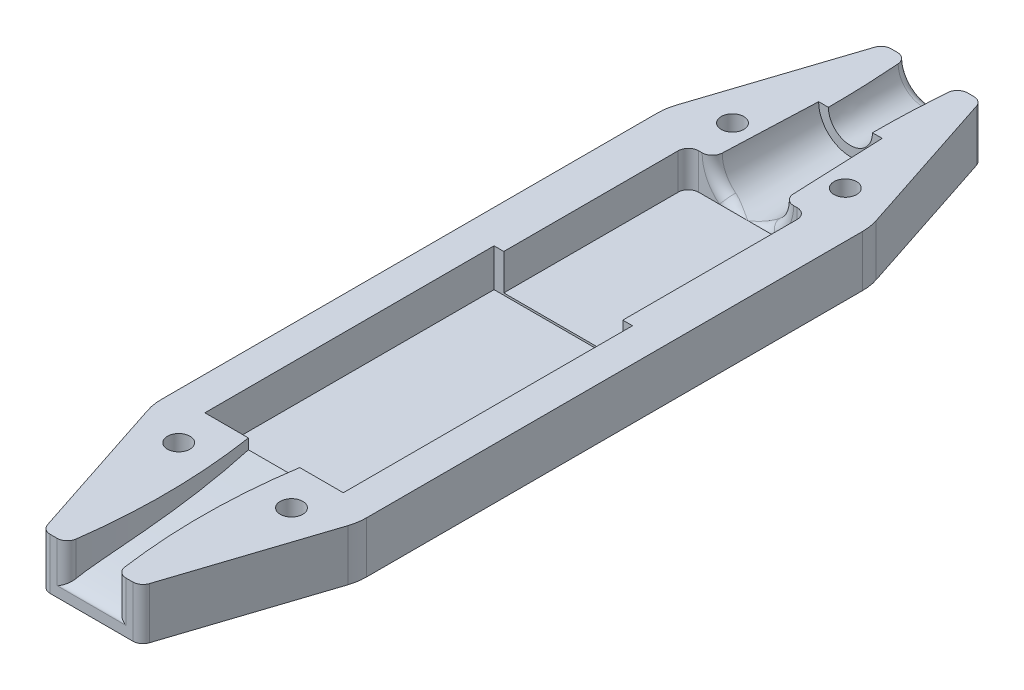
SolidWorks part; units mm, degrees
ref_plane "Ebene vorne" through (0, 0, 0) normal (0, 0, 1) x (1, 0, 0)
ref_plane "Ebene oben" through (0, 0, 0) normal (0, 1, 0) x (1, 0, 0)
ref_plane "Ebene rechts" through (0, 0, 0) normal (1, 0, 0) x (0, 0, -1)
sketch "Skizze1" plane through (0, 0, 0) normal (0, 0, 1) x (1, 0, 0)
  line L0 (0, 2.5) -> (0, -2.5)
  line L1 (-10, -2.5) -> (10, -2.5)
  line L2 (-10, -2.5) -> (-10, 2.5)
  line L3 (-10, 2.5) -> (10, 2.5)
  line L4 (10, -2.5) -> (10, 2.5)
  point P7 (0, 0)
extrude "Aufsatz-Linear austragen1" add sketch "Skizze1" along normal blind 30 contours L3 L2 L1 L0 | L1 L4 L3 L0 region at (5, 0, 0) region at (-5, 0, 0)
sketch "Skizze4" plane through (0, 0, 0) normal (0, 0, -1) x (-1, 0, 0)
  line L0 (0, 0) -> (0, 2.5)
  line L1 (10, 2.5) -> (-10, 2.5) construction
sketch "Skizze5" plane through (0, 2.5, 0) normal (0, 1, 0) x (1, 0, 0)
  line L0 (-6.75, 0) -> (6.75, 0)
  line L1 (-10, 0) -> (10, 0) construction
  line L2 (-6.75, 0) -> (-6.75, -28.2)
  line L3 (-6.75, -28.2) -> (6.75, -28.2)
  line L4 (6.75, -28.2) -> (6.75, 0)
  point P4 (0, 0)
extrude "Schnitt-Linear austragen1" cut sketch "Skizze5" against normal blind 3.7
sketch "Skizze7" plane through (0, 2.5, 0) normal (0, 1, 0) x (1, 0, 0)
  line L0 (-10, -30) -> (10, -30)
  line L1 (10, -30) -> (4.75, -46)
  line L2 (4.75, -46) -> (-4.75, -46)
  line L3 (-4.75, -46) -> (-10, -30)
  line L4 (0, -30) -> (0, -46)
  line M9 (-10, -30) -> (10, -30)
extrude "Aufsatz-Linear austragen3" add sketch "Skizze7" against normal blind 5 contours L4 L3 L2 M9 | L0 L4 L2 L1 region at (-3.8432, 2.5, 37.0508) region at (3.8432, 2.5, 37.0508)
sketch "Skizze8" plane through (0, 2.5, 0) normal (0, 1, 0) x (1, 0, 0)
  line L0 (-4.75, -46) -> (4.75, -46)
  line L1 (-6.75, -28.2) -> (6.75, -28.2) construction
  line L2 (-2.5, -46) -> (2.5, -46)
  line L3 (-2.5, -46) -> (-2.5, -28.2)
  line L4 (-2.5, -28.2) -> (2.5, -28.2)
  line L5 (2.5, -46) -> (2.5, -28.2)
  line L6 (-2.5, -46) -> (2.5, -28.2)
  line L7 (-60, -37.1) -> (60, -37.1)
  line L8 (4.75, -46) -> (-4.75, -46) construction
  line L10 (-1.8153, -37.1) -> (1.8153, -37.1)
  arc A0 (-2.5, -28.2) -> (-2.5, -46) centre (-60, -37.1) cw
  arc A1 (2.5, -46) -> (2.5, -28.2) centre (60, -37.1) cw
  point P12 (0, -46)
  point P13 (0, -46)
  point P14 (0, -37.1)
  point P15 (0, -37.1)
  line M16 (6.75, -28.2) -> (-6.75, -28.2)
extrude "Schnitt-Linear austragen3" cut sketch "Skizze8" against normal blind 4 contours A0 L7 L6 M16 | L7 A1 L6 | L0 A1 L7 L6 | L7 A0 L6 region at (0.3237, 2.5, 42.2671) region at (-1.3443, 2.5, 39.8514) region at (-0.3237, 2.5, 31.9329) region at (1.3443, 2.5, 34.3486)
sketch "Skizze9" plane through (0, 0, 0) normal (1, 0, 0) x (0, 0, -1)
  line L0 (-28.2, -1.5) -> (-28.2, 1.5)
  line L1 (-28.2, -1.2) -> (-28.2, 2.5) construction
  line L2 (-28.2, -1.5) -> (-46, -1.5)
  parabola Q0 (-42.3553, -2.8575) -> (-28.2, 1.5) focus (-45.8736, -1.5) apex (-46, -1.5)
extrude "Aufsatz-Linear austragen4" add sketch "Skizze9" along normal mid plane 6 contours Q0 L2 L0 region at (0, -0.375, 35.32)
sketch "Skizze10" plane through (0, 2.5, 0) normal (0, 1, 0) x (1, 0, 0)
  line L0 (10, -30) -> (-10, -30) construction
  line L1 (5.5, -30) -> (-5.5, -30)
  line L2 (5.5, -30) -> (5.5, -32)
  line L3 (-5.5, -30) -> (-5.5, -32)
  line L4 (-5.5, -32) -> (5.5, -32)
  circle A0 centre (5.5, -32) radius 1.1
  circle A1 centre (-5.5, -32) radius 1.1
  point P6 (0, -30)
  point P7 (0, -30)
extrude "Schnitt-Linear austragen4" cut sketch "Skizze10" against normal through all contours L4 A0 L2 | L3 A1 L4 | L4 A1 L3 | L2 A0 L4 region at (5.6556, 2.5, 32.1556) region at (5.0331, 2.5, 31.5331) region at (-5.0331, 2.5, 31.5331) region at (-5.6556, 2.5, 32.1556)
sketch "Skizze11" plane through (0, -2.5, 0) normal (0, -1, 0) x (1, 0, 0)
  line L1 (-3.0751, 32) -> (-4.2876, 34.1)
  line L2 (-4.2876, 34.1) -> (-6.7124, 34.1)
  line L3 (-6.7124, 34.1) -> (-7.9249, 32)
  line L4 (-7.9249, 32) -> (-6.7124, 29.9)
  line L5 (-6.7124, 29.9) -> (-4.2876, 29.9)
  line L6 (-4.2876, 29.9) -> (-3.0751, 32)
  line L7 (3.0751, 32) -> (4.2876, 29.9)
  line L8 (4.2876, 29.9) -> (6.7124, 29.9)
  line L9 (6.7124, 29.9) -> (7.9249, 32)
  line L10 (7.9249, 32) -> (6.7124, 34.1)
  line L11 (6.7124, 34.1) -> (4.2876, 34.1)
  line L12 (4.2876, 34.1) -> (3.0751, 32)
  circle A0 centre (-5.5, 32) radius 2.1 construction
  circle A1 centre (5.5, 32) radius 2.1 construction
extrude "Schnitt-Linear austragen5" cut sketch "Skizze11" against normal blind 1.6
sketch "Skizze12" plane through (0, 0, 0) normal (0, 0, -1) x (-1, 0, 0)
  line L1 (-10, -2.5) -> (10, -2.5)
  line L2 (-10, -2.5) -> (-10, 2.5)
  line L3 (-10, 2.5) -> (10, 2.5)
  line L4 (10, -2.5) -> (10, 2.5)
extrude "Aufsatz-Linear austragen5" add sketch "Skizze12" along normal blind 20
sketch "Skizze13" plane through (0, 2.5, 0) normal (0, 1, 0) x (1, 0, 0)
  line L0 (0, 20) -> (0, 37.0129)
  line L1 (-10, 20) -> (10, 20) construction
  line L2 (4.75, 37.0129) -> (-4.75, 37.0129)
  line L3 (4.75, 37.0129) -> (10, 20)
  line L4 (10, 20) -> (-10, 20)
  line L5 (-10, 20) -> (-4.75, 37.0129)
  point P8 (0, 37.0129)
sketch "Skizze14" plane through (0, 2.5, 0) normal (0, 1, 0) x (1, 0, 0)
  line L1 (5.8, 18) -> (-5.8, 18)
  line L2 (5.8, 18) -> (5.8, 0)
  line L3 (5.8, 0) -> (-5.8, 0)
  line L4 (-5.8, 18) -> (-5.8, 0)
  point P4 (0, 0)
extrude "Schnitt-Linear austragen6" cut sketch "Skizze14" against normal blind 3.5
sketch "Skizze16" plane through (0, 2.5, 0) normal (0, 1, 0) x (1, 0, 0)
  line L0 (0, 20) -> (0, 36)
  line L1 (-10, 20) -> (10, 20) construction
  line L2 (10, 20) -> (4.75, 36)
  line L3 (-10, 20) -> (-4.75, 36)
  line L4 (-4.75, 36) -> (4.75, 36)
  line L5 (10, 20) -> (-10, 20)
  point P12 (0, 36)
  line M13 (10, 20) -> (-10, 20)
extrude "Aufsatz-Linear austragen6" add sketch "Skizze16" against normal blind 5 contours L4 L0 L2 M13 | L4 L3 L0 M13 region at (-3.8432, 2.5, -27.0508) region at (3.8432, 2.5, -27.0508)
sketch "Skizze17" plane through (0, 2.5, 0) normal (0, 1, 0) x (1, 0, 0)
  line L0 (0, 18) -> (0, 28)
  line L1 (5.8, 18) -> (-5.8, 18) construction
  line L2 (0, 28) -> (3.1, 28)
  line L3 (3.1, 28) -> (3.5, 18)
  line L4 (5.8, 18) -> (-5.8, 18) construction
  line L5 (3.5, 18) -> (0, 18)
  line L6 (0, 28) -> (0, 36)
  line L7 (-4.75, 36) -> (4.75, 36) construction
  line L8 (0, 36) -> (2.499, 36)
  line L9 (0, 28) -> (2.15, 28)
  parabola Q0 (2.499, 36) -> (2.15, 28) focus (48, 28) apex (2.15, 28)
revolve "Schnitt-Rotation1" cut sketch "Skizze17" angle 360 about L6 region at (1.652, 2.5, -22.899) region at (1.1355, 2.5, -32.1027)
fillet "Verrundung1" radius 1 2 edges at (2.4749, 0.0251, -18) (-2.4749, 0.0251, -18)
fillet "Verrundung2" radius 1 2 edges at (-5.8, 0.75, -18) (5.8, 0.75, -18)
sketch "Skizze18" plane through (0, 2.5, 0) normal (0, 1, 0) x (1, 0, 0)
  line L0 (10, 20) -> (-10, 20)
  line L2 (5.5, 22) -> (-5.5, 22)
  line L3 (5.5, 22) -> (5.5, 20)
  line L4 (5.5, 20) -> (-5.5, 20)
  line L5 (-5.5, 22) -> (-5.5, 20)
  circle A0 centre (5.5, 22) radius 1.1
  circle A1 centre (-5.5, 22) radius 1.1
  point P8 (0, 20)
  point P9 (0, 20)
extrude "Schnitt-Linear austragen7" cut sketch "Skizze18" against normal through all contours L3 A0 L2 | L2 A0 L3 | L2 A1 L5 | L5 A1 L2 region at (5.0331, 2.5, -21.5331) region at (5.6556, 2.5, -22.1556) region at (-5.6556, 2.5, -22.1556) region at (-5.0331, 2.5, -21.5331)
sketch "Skizze19" plane through (0, -2.5, 0) normal (0, -1, 0) x (1, 0, 0)
  line L1 (-3.0751, -22) -> (-4.2876, -19.9)
  line L2 (-4.2876, -19.9) -> (-6.7124, -19.9)
  line L3 (-6.7124, -19.9) -> (-7.9249, -22)
  line L4 (-7.9249, -22) -> (-6.7124, -24.1)
  line L5 (-6.7124, -24.1) -> (-4.2876, -24.1)
  line L6 (-4.2876, -24.1) -> (-3.0751, -22)
  line L7 (7.9249, -22) -> (6.7124, -19.9)
  line L8 (6.7124, -19.9) -> (4.2876, -19.9)
  line L9 (4.2876, -19.9) -> (3.0751, -22)
  line L10 (3.0751, -22) -> (4.2876, -24.1)
  line L11 (4.2876, -24.1) -> (6.7124, -24.1)
  line L12 (6.7124, -24.1) -> (7.9249, -22)
  circle A0 centre (-5.5, -22) radius 2.1 construction
  circle A1 centre (5.5, -22) radius 2.1 construction
extrude "Schnitt-Linear austragen8" cut sketch "Skizze19" against normal blind 1.6
fillet "Verrundung3" radius 5 4 edges at (-10, 0, 30) (10, 0, -20) (10, 0, 30) (-10, 0, -20)
fillet "Verrundung4" radius 1 4 edges at (4.75, 0, 46) (4.75, 0, -36) (-4.75, 0, 46) (-4.75, 0, -36)
fillet "Verrundung5" radius 1 3 edges at (-2.5, 0.5, 46) (2.5, 0.5, 46) (0, 0.001, -36)
